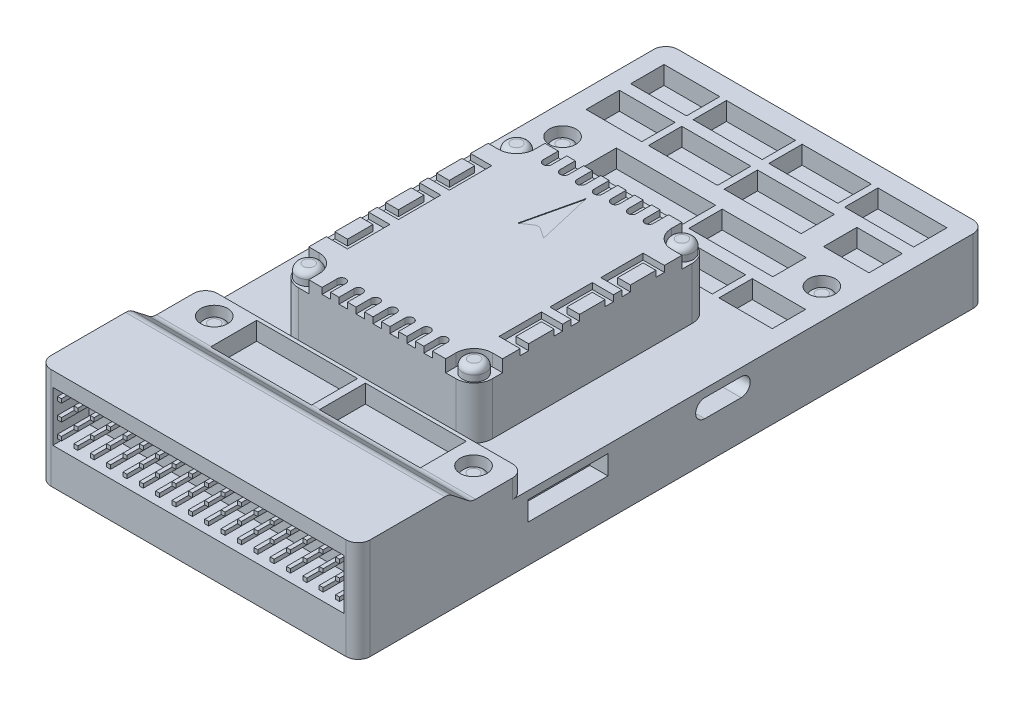
SolidWorks part; units mm, degrees
ref_plane "Front Plane" through (0, 0, 0) normal (0, 0, 1) x (1, 0, 0)
ref_plane "Top Plane" through (0, 0, 0) normal (0, 1, 0) x (1, 0, 0)
ref_plane "Right Plane" through (0, 0, 0) normal (1, 0, 0) x (0, 0, -1)
sketch "Sketch2" plane through (0, 0, 0) normal (1, 0, 0) x (0, 0, -1)
  line L0 (-51.75, 0) -> (51.75, 0)
  line L1 (55, 0) -> (-55, 0) construction
  line L2 (51.75, 0) -> (51.75, 10.7)
  line L3 (51.75, 10.7) -> (-24.25, 10.7)
  line L4 (-24.25, 10.7) -> (-24.25, 13.8)
  line L5 (-24.25, 13.8) -> (-33.05, 13.8)
  line L6 (-33.05, 13.8) -> (-36.75, 16.7)
  line L7 (-36.75, 16.7) -> (-51.75, 16.7)
  line L8 (-51.75, 16.7) -> (-51.75, 0)
  line L9 (0, 55) -> (0, -55) construction
  point P12 (0, 0)
  dimension "D1" = 103.5
  dimension "D2" = 10.7
  dimension "D3" = 16.7
  dimension "D4" = 13.8
  dimension "D5" = 8.8
  dimension "D6" = 27.5
  dimension "D7" = 15
extrude "Boss-Extrude1" add sketch "Sketch2" along normal mid plane 52.7
sketch "Sketch3" plane through (0, 10.7, 0) normal (0, 1, 0) x (1, 0, 0)
  line L0 (0, -9.185) -> (0, 9.185) construction
  line L1 (-16, 16.75) -> (16, 16.75)
  line L2 (-16, 16.75) -> (-16, -22.25)
  line L3 (-16, -22.25) -> (16, -22.25)
  line L4 (16, 16.75) -> (16, -22.25)
  line L5 (26.35, -24.25) -> (-26.35, -24.25) construction
  point P4 (0, 16.75)
  dimension "D1" = 32
  dimension "D2" = 39
  dimension "D3" = 2
extrude "Boss-Extrude2" add sketch "Sketch3" along normal blind 10.6
sketch "Sketch4" plane through (0, 10.7, 0) normal (0, 1, 0) x (1, 0, 0)
  line L0 (26.35, 51.75) -> (26.35, -24.25) construction
  line L1 (-23.35, 48.45) -> (-14.15, 48.45)
  line L2 (-23.35, 48.45) -> (-23.35, 42.95)
  line L3 (-23.35, 42.95) -> (-14.15, 42.95)
  line L4 (-14.15, 48.45) -> (-14.15, 42.95)
  line L5 (-13.05, 48.45) -> (-1.65, 48.45)
  line L6 (-13.05, 48.45) -> (-13.05, 42.95)
  line L7 (-13.05, 42.95) -> (-1.65, 42.95)
  line L8 (-1.65, 48.45) -> (-1.65, 42.95)
  line L9 (-0.55, 48.45) -> (10.85, 48.45)
  line L10 (-0.55, 48.45) -> (-0.55, 42.95)
  line L11 (-0.55, 42.95) -> (10.85, 42.95)
  line L12 (10.85, 48.45) -> (10.85, 42.95)
  line L13 (11.95, 48.45) -> (23.35, 48.45)
  line L14 (11.95, 48.45) -> (11.95, 42.95)
  line L15 (11.95, 42.95) -> (23.35, 42.95)
  line L16 (23.35, 48.45) -> (23.35, 42.95)
  line L17 (-23.35, 41.0757) -> (-14.15, 41.0757)
  line L18 (-23.35, 41.0757) -> (-23.35, 35.5757)
  line L19 (-23.35, 35.5757) -> (-14.15, 35.5757)
  line L20 (-14.15, 41.0757) -> (-14.15, 35.5757)
  line L21 (-13.05, 41.0757) -> (-1.65, 41.0757)
  line L22 (-13.05, 41.0757) -> (-13.05, 35.5757)
  line L23 (-13.05, 35.5757) -> (-1.65, 35.5757)
  line L24 (-1.65, 41.0757) -> (-1.65, 35.5757)
  line L25 (-0.55, 41.0757) -> (12.15, 41.0757)
  line L26 (-0.55, 41.0757) -> (-0.55, 35.5757)
  line L27 (-0.55, 35.5757) -> (12.15, 35.5757)
  line L28 (12.15, 41.0757) -> (12.15, 35.5757)
  line L29 (15.85, 41.0757) -> (23.35, 41.0757)
  line L30 (15.85, 41.0757) -> (15.85, 35.5757)
  line L31 (15.85, 35.5757) -> (23.35, 35.5757)
  line L32 (23.35, 41.0757) -> (23.35, 35.5757)
  line L33 (-15.35, 32.5757) -> (1.03, 32.5757)
  line L34 (-15.35, 32.5757) -> (-15.35, 27.0757)
  line L35 (-15.35, 27.0757) -> (1.03, 27.0757)
  line L36 (1.03, 32.5757) -> (1.03, 27.0757)
  line L37 (2.13, 32.5757) -> (15.98, 32.5757)
  line L38 (2.13, 32.5757) -> (2.13, 27.0757)
  line L39 (2.13, 27.0757) -> (15.98, 27.0757)
  line L40 (15.98, 32.5757) -> (15.98, 27.0757)
  line L41 (-23.35, 25.1102) -> (-14.55, 25.1102)
  line L42 (-23.35, 25.1102) -> (-23.35, 19.6102)
  line L43 (-23.35, 19.6102) -> (-14.55, 19.6102)
  line L44 (-14.55, 25.1102) -> (-14.55, 19.6102)
  line L45 (-13.45, 25.1102) -> (-4.65, 25.1102)
  line L46 (-13.45, 25.1102) -> (-13.45, 19.6102)
  line L47 (-13.45, 19.6102) -> (-4.65, 19.6102)
  line L48 (-4.65, 25.1102) -> (-4.65, 19.6102)
  line L49 (-3.55, 25.1102) -> (13.45, 25.1102)
  line L50 (-3.55, 25.1102) -> (-3.55, 19.6102)
  line L51 (-3.55, 19.6102) -> (13.45, 19.6102)
  line L52 (13.45, 25.1102) -> (13.45, 19.6102)
  line L53 (14.55, 25.1102) -> (23.35, 25.1102)
  line L54 (14.55, 25.1102) -> (14.55, 19.6102)
  line L55 (14.55, 19.6102) -> (23.35, 19.6102)
  line L56 (23.35, 25.1102) -> (23.35, 19.6102)
  line L57 (26.35, 51.75) -> (-26.35, 51.75) construction
  line L58 (-26.35, 51.75) -> (-26.35, -24.25) construction
  dimension "D1" = 3
  dimension "D2" = 3.3
  dimension "D3" = 3
  dimension "D4" = 5.5
  dimension "D5" = 1.8743
  dimension "D6" = 1.9655
  dimension "D7" = 3
  dimension "D8" = 1.1
  dimension "D9" = 1.1
  dimension "D10" = 1.1
  dimension "D11" = 11.4
  dimension "D12" = 12.7
  dimension "D13" = 7.5
  dimension "D14" = 8.8
  dimension "D15" = 1.1
  dimension "D16" = 1.1
  dimension "D17" = 1.1
  dimension "D18" = 16.38
  dimension "D19" = 1.1
  dimension "D20" = 13.85
  dimension "D21" = 10.37
extrude "Cut-Extrude1" cut sketch "Sketch4" against normal blind 3
sketch "Sketch5" plane through (0, 13.8, 0) normal (0, 1, 0) x (1, 0, 0)
  line L0 (-0.65, -24.85) -> (0.65, -24.85) construction
  line L1 (-17.3, -24.85) -> (-0.65, -24.85)
  line L2 (-17.3, -24.85) -> (-17.3, -32.45)
  line L3 (-17.3, -32.45) -> (-0.65, -32.45)
  line L4 (-0.65, -24.85) -> (-0.65, -32.45)
  line L5 (0.65, -24.85) -> (17.3, -24.85)
  line L6 (0.65, -24.85) -> (0.65, -32.45)
  line L7 (0.65, -32.45) -> (17.3, -32.45)
  line L8 (17.3, -24.85) -> (17.3, -32.45)
  line L9 (0, -11.715) -> (0, 11.715) construction
  line L10 (26.35, -24.25) -> (26.35, -33.05) construction
  point P8 (0, -24.85)
  point P14 (26.35, -28.65)
  point P15 (17.3, -28.65)
  dimension "D1" = 34.6
  dimension "D2" = 16.65
  dimension "D3" = 7.6
extrude "Cut-Extrude2" cut sketch "Sketch5" against normal blind 3
sketch "Sketch6" plane through (0, 0, 51.75) normal (0, 0, 1) x (1, 0, 0)
  line L0 (-26.35, 16.7) -> (-26.35, 0) construction
  line L1 (-24.05, 14.3) -> (24.05, 14.3)
  line L2 (-24.05, 14.3) -> (-24.05, 6)
  line L3 (-24.05, 6) -> (24.05, 6)
  line L4 (24.05, 14.3) -> (24.05, 6)
  line L5 (26.35, 16.7) -> (26.35, 0) construction
  line L6 (26.35, 16.7) -> (-26.35, 16.7) construction
  line L7 (28.985, 0) -> (-28.985, 0) construction
  dimension "D1" = 2.3
  dimension "D2" = 2.3
  dimension "D3" = 2.4
  dimension "D4" = 6
extrude "Cut-Extrude3" cut sketch "Sketch6" against normal blind 6
sketch "Sketch7" plane through (0, 0, 45.75) normal (0, 0, 1) x (1, 0, 0)
  line L0 (24.05, 14.3) -> (-24.05, 14.3) construction
  line L1 (-23.2682, 13.3817) -> (-22.6182, 13.3817)
  line L2 (-23.2682, 13.3817) -> (-23.2682, 12.7317)
  line L3 (-23.2682, 12.7317) -> (-22.6182, 12.7317)
  line L4 (-22.6182, 13.3817) -> (-22.6182, 12.7317)
  line L5 (-24.05, 14.3) -> (-24.05, 6) construction
  line L6 (-20.5682, 13.3817) -> (-20.5682, 12.7317)
  line L7 (-20.5682, 13.3817) -> (-19.9182, 13.3817)
  line L8 (-19.9182, 13.3817) -> (-19.9182, 12.7317)
  line L9 (-20.5682, 12.7317) -> (-19.9182, 12.7317)
  line L10 (-17.8682, 13.3817) -> (-17.8682, 12.7317)
  line L11 (-17.8682, 13.3817) -> (-17.2182, 13.3817)
  line L12 (-17.2182, 13.3817) -> (-17.2182, 12.7317)
  line L13 (-17.8682, 12.7317) -> (-17.2182, 12.7317)
  line L14 (-15.1682, 13.3817) -> (-15.1682, 12.7317)
  line L15 (-15.1682, 13.3817) -> (-14.5182, 13.3817)
  line L16 (-14.5182, 13.3817) -> (-14.5182, 12.7317)
  line L17 (-15.1682, 12.7317) -> (-14.5182, 12.7317)
  line L18 (-12.4682, 13.3817) -> (-12.4682, 12.7317)
  line L19 (-12.4682, 13.3817) -> (-11.8182, 13.3817)
  line L20 (-11.8182, 13.3817) -> (-11.8182, 12.7317)
  line L21 (-12.4682, 12.7317) -> (-11.8182, 12.7317)
  line L22 (-9.7682, 13.3817) -> (-9.7682, 12.7317)
  line L23 (-9.7682, 13.3817) -> (-9.1182, 13.3817)
  line L24 (-9.1182, 13.3817) -> (-9.1182, 12.7317)
  line L25 (-9.7682, 12.7317) -> (-9.1182, 12.7317)
  line L26 (-7.0682, 13.3817) -> (-7.0682, 12.7317)
  line L27 (-7.0682, 13.3817) -> (-6.4182, 13.3817)
  line L28 (-6.4182, 13.3817) -> (-6.4182, 12.7317)
  line L29 (-7.0682, 12.7317) -> (-6.4182, 12.7317)
  line L30 (-4.3682, 13.3817) -> (-4.3682, 12.7317)
  line L31 (-4.3682, 13.3817) -> (-3.7182, 13.3817)
  line L32 (-3.7182, 13.3817) -> (-3.7182, 12.7317)
  line L33 (-4.3682, 12.7317) -> (-3.7182, 12.7317)
  line L34 (-1.6682, 13.3817) -> (-1.6682, 12.7317)
  line L35 (-1.6682, 13.3817) -> (-1.0182, 13.3817)
  line L36 (-1.0182, 13.3817) -> (-1.0182, 12.7317)
  line L37 (-1.6682, 12.7317) -> (-1.0182, 12.7317)
  line L38 (1.0318, 13.3817) -> (1.0318, 12.7317)
  line L39 (1.0318, 13.3817) -> (1.6818, 13.3817)
  line L40 (1.6818, 13.3817) -> (1.6818, 12.7317)
  line L41 (1.0318, 12.7317) -> (1.6818, 12.7317)
  line L42 (3.7318, 13.3817) -> (3.7318, 12.7317)
  line L43 (3.7318, 13.3817) -> (4.3818, 13.3817)
  line L44 (4.3818, 13.3817) -> (4.3818, 12.7317)
  line L45 (3.7318, 12.7317) -> (4.3818, 12.7317)
  line L46 (6.4318, 13.3817) -> (6.4318, 12.7317)
  line L47 (6.4318, 13.3817) -> (7.0818, 13.3817)
  line L48 (7.0818, 13.3817) -> (7.0818, 12.7317)
  line L49 (6.4318, 12.7317) -> (7.0818, 12.7317)
  line L50 (9.1318, 13.3817) -> (9.1318, 12.7317)
  line L51 (9.1318, 13.3817) -> (9.7818, 13.3817)
  line L52 (9.7818, 13.3817) -> (9.7818, 12.7317)
  line L53 (9.1318, 12.7317) -> (9.7818, 12.7317)
  line L54 (11.8318, 13.3817) -> (11.8318, 12.7317)
  line L55 (11.8318, 13.3817) -> (12.4818, 13.3817)
  line L56 (12.4818, 13.3817) -> (12.4818, 12.7317)
  line L57 (11.8318, 12.7317) -> (12.4818, 12.7317)
  line L58 (14.5318, 13.3817) -> (14.5318, 12.7317)
  line L59 (14.5318, 13.3817) -> (15.1818, 13.3817)
  line L60 (15.1818, 13.3817) -> (15.1818, 12.7317)
  line L61 (14.5318, 12.7317) -> (15.1818, 12.7317)
  line L62 (17.2318, 13.3817) -> (17.2318, 12.7317)
  line L63 (17.2318, 13.3817) -> (17.8818, 13.3817)
  line L64 (17.8818, 13.3817) -> (17.8818, 12.7317)
  line L65 (17.2318, 12.7317) -> (17.8818, 12.7317)
  line L66 (19.9318, 13.3817) -> (19.9318, 12.7317)
  line L67 (19.9318, 13.3817) -> (20.5818, 13.3817)
  line L68 (20.5818, 13.3817) -> (20.5818, 12.7317)
  line L69 (19.9318, 12.7317) -> (20.5818, 12.7317)
  line L70 (22.6318, 13.3817) -> (22.6318, 12.7317)
  line L71 (22.6318, 13.3817) -> (23.2818, 13.3817)
  line L72 (23.2818, 13.3817) -> (23.2818, 12.7317)
  line L73 (22.6318, 12.7317) -> (23.2818, 12.7317)
  line L74 (-20.5682, 10.6817) -> (-20.5682, 10.0317)
  line L75 (-20.5682, 10.6817) -> (-19.9182, 10.6817)
  line L76 (-19.9182, 10.6817) -> (-19.9182, 10.0317)
  line L77 (-20.5682, 10.0317) -> (-19.9182, 10.0317)
  line L78 (-17.8682, 10.6817) -> (-17.8682, 10.0317)
  line L79 (-17.8682, 10.6817) -> (-17.2182, 10.6817)
  line L80 (-17.2182, 10.6817) -> (-17.2182, 10.0317)
  line L81 (-17.8682, 10.0317) -> (-17.2182, 10.0317)
  line L82 (-15.1682, 10.6817) -> (-15.1682, 10.0317)
  line L83 (-15.1682, 10.6817) -> (-14.5182, 10.6817)
  line L84 (-14.5182, 10.6817) -> (-14.5182, 10.0317)
  line L85 (-15.1682, 10.0317) -> (-14.5182, 10.0317)
  line L86 (-12.4682, 10.6817) -> (-12.4682, 10.0317)
  line L87 (-12.4682, 10.6817) -> (-11.8182, 10.6817)
  line L88 (-11.8182, 10.6817) -> (-11.8182, 10.0317)
  line L89 (-12.4682, 10.0317) -> (-11.8182, 10.0317)
  line L90 (-9.7682, 10.6817) -> (-9.7682, 10.0317)
  line L91 (-9.7682, 10.6817) -> (-9.1182, 10.6817)
  line L92 (-9.1182, 10.6817) -> (-9.1182, 10.0317)
  line L93 (-9.7682, 10.0317) -> (-9.1182, 10.0317)
  line L94 (-7.0682, 10.6817) -> (-7.0682, 10.0317)
  line L95 (-7.0682, 10.6817) -> (-6.4182, 10.6817)
  line L96 (-6.4182, 10.6817) -> (-6.4182, 10.0317)
  line L97 (-7.0682, 10.0317) -> (-6.4182, 10.0317)
  line L98 (-4.3682, 10.6817) -> (-4.3682, 10.0317)
  line L99 (-4.3682, 10.6817) -> (-3.7182, 10.6817)
  line L100 (-3.7182, 10.6817) -> (-3.7182, 10.0317)
  line L101 (-4.3682, 10.0317) -> (-3.7182, 10.0317)
  line L102 (-1.6682, 10.6817) -> (-1.6682, 10.0317)
  line L103 (-1.6682, 10.6817) -> (-1.0182, 10.6817)
  line L104 (-1.0182, 10.6817) -> (-1.0182, 10.0317)
  line L105 (-1.6682, 10.0317) -> (-1.0182, 10.0317)
  line L106 (1.0318, 10.6817) -> (1.0318, 10.0317)
  line L107 (1.0318, 10.6817) -> (1.6818, 10.6817)
  line L108 (1.6818, 10.6817) -> (1.6818, 10.0317)
  line L109 (1.0318, 10.0317) -> (1.6818, 10.0317)
  line L110 (3.7318, 10.6817) -> (3.7318, 10.0317)
  line L111 (3.7318, 10.6817) -> (4.3818, 10.6817)
  line L112 (4.3818, 10.6817) -> (4.3818, 10.0317)
  line L113 (3.7318, 10.0317) -> (4.3818, 10.0317)
  line L114 (6.4318, 10.6817) -> (6.4318, 10.0317)
  line L115 (6.4318, 10.6817) -> (7.0818, 10.6817)
  line L116 (7.0818, 10.6817) -> (7.0818, 10.0317)
  line L117 (6.4318, 10.0317) -> (7.0818, 10.0317)
  line L118 (9.1318, 10.6817) -> (9.1318, 10.0317)
  line L119 (9.1318, 10.6817) -> (9.7818, 10.6817)
  line L120 (9.7818, 10.6817) -> (9.7818, 10.0317)
  line L121 (9.1318, 10.0317) -> (9.7818, 10.0317)
  line L122 (11.8318, 10.6817) -> (11.8318, 10.0317)
  line L123 (11.8318, 10.6817) -> (12.4818, 10.6817)
  line L124 (12.4818, 10.6817) -> (12.4818, 10.0317)
  line L125 (11.8318, 10.0317) -> (12.4818, 10.0317)
  line L126 (14.5318, 10.6817) -> (14.5318, 10.0317)
  line L127 (14.5318, 10.6817) -> (15.1818, 10.6817)
  line L128 (15.1818, 10.6817) -> (15.1818, 10.0317)
  line L129 (14.5318, 10.0317) -> (15.1818, 10.0317)
  line L130 (17.2318, 10.6817) -> (17.2318, 10.0317)
  line L131 (17.2318, 10.6817) -> (17.8818, 10.6817)
  line L132 (17.8818, 10.6817) -> (17.8818, 10.0317)
  line L133 (17.2318, 10.0317) -> (17.8818, 10.0317)
  line L134 (19.9318, 10.6817) -> (19.9318, 10.0317)
  line L135 (19.9318, 10.6817) -> (20.5818, 10.6817)
  line L136 (20.5818, 10.6817) -> (20.5818, 10.0317)
  line L137 (19.9318, 10.0317) -> (20.5818, 10.0317)
  line L138 (22.6318, 10.6817) -> (22.6318, 10.0317)
  line L139 (22.6318, 10.6817) -> (23.2818, 10.6817)
  line L140 (23.2818, 10.6817) -> (23.2818, 10.0317)
  line L141 (22.6318, 10.0317) -> (23.2818, 10.0317)
  line L142 (-20.5682, 7.9817) -> (-20.5682, 7.3317)
  line L143 (-20.5682, 7.9817) -> (-19.9182, 7.9817)
  line L144 (-19.9182, 7.9817) -> (-19.9182, 7.3317)
  line L145 (-20.5682, 7.3317) -> (-19.9182, 7.3317)
  line L146 (-17.8682, 7.9817) -> (-17.8682, 7.3317)
  line L147 (-17.8682, 7.9817) -> (-17.2182, 7.9817)
  line L148 (-17.2182, 7.9817) -> (-17.2182, 7.3317)
  line L149 (-17.8682, 7.3317) -> (-17.2182, 7.3317)
  line L150 (-15.1682, 7.9817) -> (-15.1682, 7.3317)
  line L151 (-15.1682, 7.9817) -> (-14.5182, 7.9817)
  line L152 (-14.5182, 7.9817) -> (-14.5182, 7.3317)
  line L153 (-15.1682, 7.3317) -> (-14.5182, 7.3317)
  line L154 (-12.4682, 7.9817) -> (-12.4682, 7.3317)
  line L155 (-12.4682, 7.9817) -> (-11.8182, 7.9817)
  line L156 (-11.8182, 7.9817) -> (-11.8182, 7.3317)
  line L157 (-12.4682, 7.3317) -> (-11.8182, 7.3317)
  line L158 (-9.7682, 7.9817) -> (-9.7682, 7.3317)
  line L159 (-9.7682, 7.9817) -> (-9.1182, 7.9817)
  line L160 (-9.1182, 7.9817) -> (-9.1182, 7.3317)
  line L161 (-9.7682, 7.3317) -> (-9.1182, 7.3317)
  line L162 (-7.0682, 7.9817) -> (-7.0682, 7.3317)
  line L163 (-7.0682, 7.9817) -> (-6.4182, 7.9817)
  line L164 (-6.4182, 7.9817) -> (-6.4182, 7.3317)
  line L165 (-7.0682, 7.3317) -> (-6.4182, 7.3317)
  line L166 (-4.3682, 7.9817) -> (-4.3682, 7.3317)
  line L167 (-4.3682, 7.9817) -> (-3.7182, 7.9817)
  line L168 (-3.7182, 7.9817) -> (-3.7182, 7.3317)
  line L169 (-4.3682, 7.3317) -> (-3.7182, 7.3317)
  line L170 (-1.6682, 7.9817) -> (-1.6682, 7.3317)
  line L171 (-1.6682, 7.9817) -> (-1.0182, 7.9817)
  line L172 (-1.0182, 7.9817) -> (-1.0182, 7.3317)
  line L173 (-1.6682, 7.3317) -> (-1.0182, 7.3317)
  line L174 (1.0318, 7.9817) -> (1.0318, 7.3317)
  line L175 (1.0318, 7.9817) -> (1.6818, 7.9817)
  line L176 (1.6818, 7.9817) -> (1.6818, 7.3317)
  line L177 (1.0318, 7.3317) -> (1.6818, 7.3317)
  line L178 (3.7318, 7.9817) -> (3.7318, 7.3317)
  line L179 (3.7318, 7.9817) -> (4.3818, 7.9817)
  line L180 (4.3818, 7.9817) -> (4.3818, 7.3317)
  line L181 (3.7318, 7.3317) -> (4.3818, 7.3317)
  line L182 (6.4318, 7.9817) -> (6.4318, 7.3317)
  line L183 (6.4318, 7.9817) -> (7.0818, 7.9817)
  line L184 (7.0818, 7.9817) -> (7.0818, 7.3317)
  line L185 (6.4318, 7.3317) -> (7.0818, 7.3317)
  line L186 (9.1318, 7.9817) -> (9.1318, 7.3317)
  line L187 (9.1318, 7.9817) -> (9.7818, 7.9817)
  line L188 (9.7818, 7.9817) -> (9.7818, 7.3317)
  line L189 (9.1318, 7.3317) -> (9.7818, 7.3317)
  line L190 (11.8318, 7.9817) -> (11.8318, 7.3317)
  line L191 (11.8318, 7.9817) -> (12.4818, 7.9817)
  line L192 (12.4818, 7.9817) -> (12.4818, 7.3317)
  line L193 (11.8318, 7.3317) -> (12.4818, 7.3317)
  line L194 (14.5318, 7.9817) -> (14.5318, 7.3317)
  line L195 (14.5318, 7.9817) -> (15.1818, 7.9817)
  line L196 (15.1818, 7.9817) -> (15.1818, 7.3317)
  line L197 (14.5318, 7.3317) -> (15.1818, 7.3317)
  line L198 (17.2318, 7.9817) -> (17.2318, 7.3317)
  line L199 (17.2318, 7.9817) -> (17.8818, 7.9817)
  line L200 (17.8818, 7.9817) -> (17.8818, 7.3317)
  line L201 (17.2318, 7.3317) -> (17.8818, 7.3317)
  line L202 (19.9318, 7.9817) -> (19.9318, 7.3317)
  line L203 (19.9318, 7.9817) -> (20.5818, 7.9817)
  line L204 (20.5818, 7.9817) -> (20.5818, 7.3317)
  line L205 (19.9318, 7.3317) -> (20.5818, 7.3317)
  line L206 (22.6318, 7.9817) -> (22.6318, 7.3317)
  line L207 (22.6318, 7.9817) -> (23.2818, 7.9817)
  line L208 (23.2818, 7.9817) -> (23.2818, 7.3317)
  line L209 (22.6318, 7.3317) -> (23.2818, 7.3317)
  line L210 (-23.2682, 10.6817) -> (-23.2682, 10.0317)
  line L211 (-23.2682, 10.6817) -> (-22.6182, 10.6817)
  line L212 (-22.6182, 10.6817) -> (-22.6182, 10.0317)
  line L213 (-23.2682, 10.0317) -> (-22.6182, 10.0317)
  line L214 (-23.2682, 7.9817) -> (-23.2682, 7.3317)
  line L215 (-23.2682, 7.9817) -> (-22.6182, 7.9817)
  line L216 (-22.6182, 7.9817) -> (-22.6182, 7.3317)
  line L217 (-23.2682, 7.3317) -> (-22.6182, 7.3317)
  dimension "D1" = 0.65
  dimension "D2" = 0.9183
  dimension "D3" = 0.7818
  dimension "D6" = 2.05
  dimension "D7" = 2.05
  dimension "D4" = 18
  dimension "D5" = 3
extrude "Boss-Extrude3" add sketch "Sketch7" along normal blind 6
sketch "Sketch8" plane through (-26.35, 0, 0) normal (-1, 0, 0) x (0, 0, 1)
  line L0 (51.75, 16.7) -> (51.75, 0) construction
  line L1 (10.45, 9.4) -> (23.75, 9.4)
  line L2 (10.45, 9.4) -> (10.45, 6.1)
  line L3 (10.45, 6.1) -> (23.75, 6.1)
  line L4 (23.75, 9.4) -> (23.75, 6.1)
  line L5 (-51.75, 10.7) -> (24.25, 10.7) construction
  dimension "D1" = 3.3
  dimension "D2" = 13.3
  dimension "D3" = 28
  dimension "D4" = 1.3
extrude "Cut-Extrude4" cut sketch "Sketch8" against normal blind 3
sketch "Sketch9" plane through (26.35, 0, 0) normal (1, 0, 0) x (0, 0, -1)
  line L0 (51.75, 10.7) -> (-24.25, 10.7) construction
  line L1 (-23.75, 9.4) -> (-10.5, 9.4)
  line L2 (-23.75, 9.4) -> (-23.75, 6.2)
  line L3 (-23.75, 6.2) -> (-10.5, 6.2)
  line L4 (-10.5, 9.4) -> (-10.5, 6.2)
  line L5 (-51.75, 16.7) -> (-51.75, 0) construction
  line L6 (5.47, 7.9) -> (11.47, 7.9) construction
  line L7 (5.47, 9.4) -> (11.47, 9.4)
  line L8 (5.47, 6.4) -> (11.47, 6.4)
  arc A0 (5.47, 9.4) -> (5.47, 6.4) centre (5.47, 7.9) ccw
  arc A1 (11.47, 6.4) -> (11.47, 9.4) centre (11.47, 7.9) ccw
  point P10 (8.47, 7.9)
  dimension "D1" = 13.25
  dimension "D2" = 3.2
  dimension "D3" = 1.3
  dimension "D4" = 28
  dimension "D5" = 6
  dimension "D6" = 3
  dimension "D7" = 15.97
  dimension "D8" = 1.3
extrude "Cut-Extrude5" cut sketch "Sketch9" against normal blind 3
sketch "Sketch10" plane through (0, 0, 0) normal (0, -1, 0) x (1, 0, 0)
  line L0 (0, -11.715) -> (0, 11.715) construction
  line L1 (-21.4, 27.75) -> (21.4, 27.75) construction
  line L2 (-21.4, 27.75) -> (-21.4, -29.75) construction
  line L3 (-21.4, -29.75) -> (21.4, -29.75) construction
  line L4 (21.4, 27.75) -> (21.4, -29.75) construction
  line L6 (26.35, -51.75) -> (-26.35, -51.75) construction
  circle A0 centre (-21.4, 27.75) radius 1.25
  circle A1 centre (21.4, 27.75) radius 1.25
  circle A2 centre (21.4, -29.75) radius 1.25
  circle A3 centre (-21.4, -29.75) radius 1.25
  point P8 (0, 27.75)
  dimension "D3" = 2.5
  dimension "D1" = 57.5
  dimension "D2" = 42.8
  dimension "D4" = 22
extrude "Cut-Extrude6" cut sketch "Sketch10" against normal blind 3
sketch "Sketch11" plane through (0, 0, 0) normal (0, -1, 0) x (1, 0, 0)
  line L0 (0, -11.715) -> (0, 11.715) construction
  line L1 (-12.25, 17.75) -> (12.25, 17.75) construction
  line L2 (-12.25, 17.75) -> (-12.25, -13.75) construction
  line L3 (-12.25, -13.75) -> (12.25, -13.75) construction
  line L4 (12.25, 17.75) -> (12.25, -13.75) construction
  line L5 (26.35, -51.75) -> (-26.35, -51.75) construction
  circle A0 centre (-12.25, 17.75) radius 2.2
  circle A1 centre (12.25, 17.75) radius 2.2
  circle A2 centre (12.25, -13.75) radius 2.2
  circle A3 centre (-12.25, -13.75) radius 2.2
  point P4 (0, 17.75)
  dimension "D1" = 4.4
  dimension "D2" = 31.5
  dimension "D3" = 24.5
  dimension "D4" = 38
extrude "Cut-Extrude7" cut sketch "Sketch11" against normal blind 3
fillet "Fillet1" radius 2 8 edges at (0, 13.8, 33.05) (0, 16.7, 36.75) (26.35, 5.35, -51.75) (26.35, 8.35, 51.75) (-26.35, 8.35, 51.75) (-26.35, 5.35, -51.75) (26.35, 12.25, 24.25) (-26.35, 12.25, 24.25)
fillet "Fillet2" radius 3 4 edges at (-16, 16, -16.75) (-16, 16, 22.25) (16, 16, 22.25) (16, 16, -16.75)
sketch "Sketch12" plane through (0, 21.3, 0) normal (0, 1, 0) x (1, 0, 0)
  line L0 (-8.4, 16.75) -> (-8.4, 14.25) construction
  line L1 (13, 16.75) -> (-13, 16.75) construction
  line L2 (-7.7, 16.75) -> (-7.7, 14.25)
  line L3 (-9.1, 16.75) -> (-9.1, 14.25)
  line L4 (-5.6, 16.75) -> (-5.6, 14.25) construction
  line L5 (-4.9, 16.75) -> (-4.9, 14.25)
  line L6 (-6.3, 16.75) -> (-6.3, 14.25)
  line L7 (-2.8, 16.75) -> (-2.8, 14.25) construction
  line L8 (-2.1, 16.75) -> (-2.1, 14.25)
  line L9 (-3.5, 16.75) -> (-3.5, 14.25)
  line L10 (0, 16.75) -> (0, 14.25) construction
  line L11 (0.7, 16.75) -> (0.7, 14.25)
  line L12 (-0.7, 16.75) -> (-0.7, 14.25)
  line L13 (2.8, 16.75) -> (2.8, 14.25) construction
  line L14 (3.5, 16.75) -> (3.5, 14.25)
  line L15 (2.1, 16.75) -> (2.1, 14.25)
  line L16 (5.6, 16.75) -> (5.6, 14.25) construction
  line L17 (6.3, 16.75) -> (6.3, 14.25)
  line L18 (4.9, 16.75) -> (4.9, 14.25)
  line L19 (8.4, 16.75) -> (8.4, 14.25) construction
  line L20 (9.1, 16.75) -> (9.1, 14.25)
  line L21 (7.7, 16.75) -> (7.7, 14.25)
  line L22 (0, -11.715) -> (0, 11.715) construction
  line L23 (13, 16.75) -> (-13, 16.75) construction
  line L26 (-13.7846, -2.75) -> (10.4131, -2.75) construction
  line L27 (-16, 13.75) -> (-16, -19.25) construction
  line L28 (-8.4, -22.25) -> (-8.4, -19.75) construction
  line L29 (-7.7, -22.25) -> (-7.7, -19.75)
  line L30 (-9.1, -22.25) -> (-9.1, -19.75)
  line L31 (-5.6, -22.25) -> (-5.6, -19.75) construction
  line L32 (-4.9, -22.25) -> (-4.9, -19.75)
  line L33 (-6.3, -22.25) -> (-6.3, -19.75)
  line L34 (-2.8, -22.25) -> (-2.8, -19.75) construction
  line L35 (-2.1, -22.25) -> (-2.1, -19.75)
  line L36 (-3.5, -22.25) -> (-3.5, -19.75)
  line L37 (0, -22.25) -> (0, -19.75) construction
  line L38 (0.7, -22.25) -> (0.7, -19.75)
  line L39 (-0.7, -22.25) -> (-0.7, -19.75)
  line L40 (2.8, -22.25) -> (2.8, -19.75) construction
  line L41 (3.5, -22.25) -> (3.5, -19.75)
  line L42 (2.1, -22.25) -> (2.1, -19.75)
  line L43 (5.6, -22.25) -> (5.6, -19.75) construction
  line L44 (6.3, -22.25) -> (6.3, -19.75)
  line L45 (4.9, -22.25) -> (4.9, -19.75)
  line L46 (8.4, -22.25) -> (8.4, -19.75) construction
  line L47 (9.1, -22.25) -> (9.1, -19.75)
  line L48 (7.7, -22.25) -> (7.7, -19.75)
  arc A0 (-7.7, 16.75) -> (-9.1, 16.75) centre (-8.4, 16.75) ccw
  arc A1 (-9.1, 14.25) -> (-7.7, 14.25) centre (-8.4, 14.25) ccw
  arc A2 (-4.9, 16.75) -> (-6.3, 16.75) centre (-5.6, 16.75) ccw
  arc A3 (-6.3, 14.25) -> (-4.9, 14.25) centre (-5.6, 14.25) ccw
  arc A4 (-2.1, 16.75) -> (-3.5, 16.75) centre (-2.8, 16.75) ccw
  arc A5 (-3.5, 14.25) -> (-2.1, 14.25) centre (-2.8, 14.25) ccw
  arc A6 (0.7, 16.75) -> (-0.7, 16.75) centre (0, 16.75) ccw
  arc A7 (-0.7, 14.25) -> (0.7, 14.25) centre (0, 14.25) ccw
  arc A8 (3.5, 16.75) -> (2.1, 16.75) centre (2.8, 16.75) ccw
  arc A9 (2.1, 14.25) -> (3.5, 14.25) centre (2.8, 14.25) ccw
  arc A10 (6.3, 16.75) -> (4.9, 16.75) centre (5.6, 16.75) ccw
  arc A11 (4.9, 14.25) -> (6.3, 14.25) centre (5.6, 14.25) ccw
  arc A12 (9.1, 16.75) -> (7.7, 16.75) centre (8.4, 16.75) ccw
  arc A13 (7.7, 14.25) -> (9.1, 14.25) centre (8.4, 14.25) ccw
  arc A14 (-7.7, -22.25) -> (-9.1, -22.25) centre (-8.4, -22.25) cw
  arc A15 (-9.1, -19.75) -> (-7.7, -19.75) centre (-8.4, -19.75) cw
  arc A16 (-4.9, -22.25) -> (-6.3, -22.25) centre (-5.6, -22.25) cw
  arc A17 (-6.3, -19.75) -> (-4.9, -19.75) centre (-5.6, -19.75) cw
  arc A18 (-2.1, -22.25) -> (-3.5, -22.25) centre (-2.8, -22.25) cw
  arc A19 (-3.5, -19.75) -> (-2.1, -19.75) centre (-2.8, -19.75) cw
  arc A20 (0.7, -22.25) -> (-0.7, -22.25) centre (0, -22.25) cw
  arc A21 (-0.7, -19.75) -> (0.7, -19.75) centre (0, -19.75) cw
  arc A22 (3.5, -22.25) -> (2.1, -22.25) centre (2.8, -22.25) cw
  arc A23 (2.1, -19.75) -> (3.5, -19.75) centre (2.8, -19.75) cw
  arc A24 (6.3, -22.25) -> (4.9, -22.25) centre (5.6, -22.25) cw
  arc A25 (4.9, -19.75) -> (6.3, -19.75) centre (5.6, -19.75) cw
  arc A26 (9.1, -22.25) -> (7.7, -22.25) centre (8.4, -22.25) cw
  arc A27 (7.7, -19.75) -> (9.1, -19.75) centre (8.4, -19.75) cw
  point P4 (-8.4, 15.5)
  point P12 (-5.6, 15.5)
  point P19 (-2.8, 15.5)
  point P26 (0, 15.5)
  point P33 (2.8, 15.5)
  point P40 (5.6, 15.5)
  point P47 (8.4, 15.5)
  point P58 (-16, -2.75)
  point P63 (-8.4, -21)
  point P70 (-5.6, -21)
  point P77 (-2.8, -21)
  point P84 (0, -21)
  point P91 (2.8, -21)
  point P98 (5.6, -21)
  point P105 (8.4, -21)
  dimension "D1" = 1.4
  dimension "D2" = 2.5
  dimension "D4" = 1.4
  dimension "D3" = 7
extrude "Cut-Extrude8" cut sketch "Sketch12" against normal blind 1
sketch "Sketch13" plane through (0, 21.3, 0) normal (0, 1, 0) x (1, 0, 0)
  line L0 (-16, 13.75) -> (-16, -19.25) construction
  line L1 (-18.8, 9.15) -> (-12.5, 9.15)
  line L2 (-18.8, 9.15) -> (-18.8, 2.15)
  line L3 (-18.8, 2.15) -> (-12.5, 2.15)
  line L4 (-12.5, 9.15) -> (-12.5, 2.15)
  line L5 (-17.4, 7.75) -> (-13.9, 7.75)
  line L6 (-17.4, 7.75) -> (-17.4, 3.55)
  line L7 (-17.4, 3.55) -> (-13.9, 3.55)
  line L8 (-13.9, 7.75) -> (-13.9, 3.55)
  line L9 (-18.8, 0.75) -> (-12.5, 0.75)
  line L10 (-18.8, 0.75) -> (-18.8, -6.25)
  line L11 (-18.8, -6.25) -> (-12.5, -6.25)
  line L12 (-12.5, 0.75) -> (-12.5, -6.25)
  line L13 (-17.4, -0.65) -> (-13.9, -0.65)
  line L14 (-17.4, -0.65) -> (-17.4, -4.85)
  line L15 (-17.4, -4.85) -> (-13.9, -4.85)
  line L16 (-13.9, -0.65) -> (-13.9, -4.85)
  line L17 (-18.8, -7.65) -> (-12.5, -7.65)
  line L18 (-18.8, -7.65) -> (-18.8, -14.65)
  line L19 (-18.8, -14.65) -> (-12.5, -14.65)
  line L20 (-12.5, -7.65) -> (-12.5, -14.65)
  line L21 (-17.4, -9.05) -> (-13.9, -9.05)
  line L22 (-17.4, -9.05) -> (-17.4, -13.25)
  line L23 (-17.4, -13.25) -> (-13.9, -13.25)
  line L24 (-13.9, -9.05) -> (-13.9, -13.25)
  line L26 (-16, 13.75) -> (-16, -19.25) construction
  line L27 (0, 12.7067) -> (0, -15.9505) construction
  line L28 (0, -11.715) -> (0, 11.715) construction
  line L29 (13.9, -9.05) -> (13.9, -13.25)
  line L30 (17.4, -13.25) -> (13.9, -13.25)
  line L31 (17.4, -9.05) -> (17.4, -13.25)
  line L32 (17.4, -9.05) -> (13.9, -9.05)
  line L33 (12.5, -7.65) -> (12.5, -14.65)
  line L34 (18.8, -14.65) -> (12.5, -14.65)
  line L35 (18.8, -7.65) -> (18.8, -14.65)
  line L36 (18.8, -7.65) -> (12.5, -7.65)
  line L37 (13.9, -0.65) -> (13.9, -4.85)
  line L38 (17.4, -4.85) -> (13.9, -4.85)
  line L39 (17.4, -0.65) -> (17.4, -4.85)
  line L40 (17.4, -0.65) -> (13.9, -0.65)
  line L41 (12.5, 0.75) -> (12.5, -6.25)
  line L42 (18.8, -6.25) -> (12.5, -6.25)
  line L43 (18.8, 0.75) -> (18.8, -6.25)
  line L44 (18.8, 0.75) -> (12.5, 0.75)
  line L45 (13.9, 7.75) -> (13.9, 3.55)
  line L46 (17.4, 3.55) -> (13.9, 3.55)
  line L47 (17.4, 7.75) -> (17.4, 3.55)
  line L48 (17.4, 7.75) -> (13.9, 7.75)
  line L49 (12.5, 9.15) -> (12.5, 2.15)
  line L50 (18.8, 2.15) -> (12.5, 2.15)
  line L51 (18.8, 9.15) -> (18.8, 2.15)
  line L52 (18.8, 9.15) -> (12.5, 9.15)
  point P10 (-16, -2.75)
  point P27 (-18.8, -2.75)
  dimension "D1" = 1.4
  dimension "D2" = 1.4
  dimension "D3" = 1.4
  dimension "D4" = 1.4
  dimension "D5" = 1.4
  dimension "D7" = 1.4
  dimension "D8" = 7
  dimension "D9" = 3.5
  dimension "D6" = 3
extrude "Cut-Extrude9" cut sketch "Sketch13" against normal blind 1
sketch "Sketch14" plane through (0, 21.3, 0) normal (0, 1, 0) x (1, 0, 0)
  line L0 (-16, 12.05) -> (-14.3, 12.05)
  line L1 (-16, 13.75) -> (-16, 9.15) construction
  line L2 (-11.3, 15.05) -> (-11.3, 16.75)
  line L3 (-9.1, 16.75) -> (-13, 16.75) construction
  line L4 (-16, 13.75) -> (-16, -19.25) construction
  line L5 (-12.5, -2.75) -> (12.5, -2.75) construction
  line L6 (-12.5, -6.25) -> (-12.5, 0.75) construction
  line L7 (12.5, 0.75) -> (12.5, -6.25) construction
  line L8 (0, 12.05) -> (0, -14.6697) construction
  line L9 (0, -11.715) -> (0, 11.715) construction
  line L10 (11.3, 15.05) -> (11.3, 16.75)
  line L11 (16, 12.05) -> (14.3, 12.05)
  line L12 (16, -17.55) -> (14.3, -17.55)
  line L13 (11.3, -20.55) -> (11.3, -22.25)
  line L14 (-11.3, -20.55) -> (-11.3, -22.25)
  line L15 (-16, -17.55) -> (-14.3, -17.55)
  line L86 (12.5, 9.15) -> (16, 9.15)
  line L87 (16, 9.15) -> (16, 13.75)
  line L88 (13, 16.75) -> (9.1, 16.75)
  line L89 (9.1, 16.75) -> (9.1, 14.25)
  line L90 (7.7, 14.25) -> (7.7, 16.75)
  line L91 (7.7, 16.75) -> (6.3, 16.75)
  line L92 (6.3, 16.75) -> (6.3, 14.25)
  line L93 (4.9, 14.25) -> (4.9, 16.75)
  line L94 (4.9, 16.75) -> (3.5, 16.75)
  line L95 (3.5, 16.75) -> (3.5, 14.25)
  line L96 (2.1, 14.25) -> (2.1, 16.75)
  line L97 (2.1, 16.75) -> (0.7, 16.75)
  line L98 (0.7, 16.75) -> (0.7, 14.25)
  line L99 (-0.7, 14.25) -> (-0.7, 16.75)
  line L100 (-0.7, 16.75) -> (-2.1, 16.75)
  line L101 (-2.1, 16.75) -> (-2.1, 14.25)
  line L102 (-3.5, 14.25) -> (-3.5, 16.75)
  line L103 (-3.5, 16.75) -> (-4.9, 16.75)
  line L104 (-4.9, 16.75) -> (-4.9, 14.25)
  line L105 (-6.3, 14.25) -> (-6.3, 16.75)
  line L106 (-6.3, 16.75) -> (-7.7, 16.75)
  line L107 (-7.7, 16.75) -> (-7.7, 14.25)
  line L108 (-9.1, 14.25) -> (-9.1, 16.75)
  line L109 (-9.1, 16.75) -> (-13, 16.75)
  line L110 (-16, 13.75) -> (-16, 9.15)
  line L111 (-16, 9.15) -> (-12.5, 9.15)
  line L112 (-12.5, 9.15) -> (-12.5, 2.15)
  line L113 (-12.5, 2.15) -> (-16, 2.15)
  line L114 (-16, 2.15) -> (-16, 0.75)
  line L115 (-16, 0.75) -> (-12.5, 0.75)
  line L116 (-12.5, 0.75) -> (-12.5, -6.25)
  line L117 (-12.5, -6.25) -> (-16, -6.25)
  line L118 (-16, -6.25) -> (-16, -7.65)
  line L119 (-16, -7.65) -> (-12.5, -7.65)
  line L120 (-12.5, -7.65) -> (-12.5, -14.65)
  line L121 (-12.5, -14.65) -> (-16, -14.65)
  line L122 (-16, -14.65) -> (-16, -19.25)
  line L123 (-13, -22.25) -> (-9.1, -22.25)
  line L124 (-9.1, -22.25) -> (-9.1, -19.75)
  line L125 (-7.7, -19.75) -> (-7.7, -22.25)
  line L126 (-7.7, -22.25) -> (-6.3, -22.25)
  line L127 (-6.3, -22.25) -> (-6.3, -19.75)
  line L128 (-4.9, -19.75) -> (-4.9, -22.25)
  line L129 (-4.9, -22.25) -> (-3.5, -22.25)
  line L130 (-3.5, -22.25) -> (-3.5, -19.75)
  line L131 (-2.1, -19.75) -> (-2.1, -22.25)
  line L132 (-2.1, -22.25) -> (-0.7, -22.25)
  line L133 (-0.7, -22.25) -> (-0.7, -19.75)
  line L134 (0.7, -19.75) -> (0.7, -22.25)
  line L135 (0.7, -22.25) -> (2.1, -22.25)
  line L136 (2.1, -22.25) -> (2.1, -19.75)
  line L137 (3.5, -19.75) -> (3.5, -22.25)
  line L138 (3.5, -22.25) -> (4.9, -22.25)
  line L139 (4.9, -22.25) -> (4.9, -19.75)
  line L140 (6.3, -19.75) -> (6.3, -22.25)
  line L141 (6.3, -22.25) -> (7.7, -22.25)
  line L142 (7.7, -22.25) -> (7.7, -19.75)
  line L143 (9.1, -19.75) -> (9.1, -22.25)
  line L144 (9.1, -22.25) -> (13, -22.25)
  line L145 (16, -19.25) -> (16, -14.65)
  line L146 (16, -14.65) -> (12.5, -14.65)
  line L147 (12.5, -14.65) -> (12.5, -7.65)
  line L148 (12.5, -7.65) -> (16, -7.65)
  line L149 (16, -7.65) -> (16, -6.25)
  line L150 (16, -6.25) -> (12.5, -6.25)
  line L151 (12.5, -6.25) -> (12.5, 0.75)
  line L152 (12.5, 0.75) -> (16, 0.75)
  line L153 (16, 0.75) -> (16, 2.15)
  line L154 (16, 2.15) -> (12.5, 2.15)
  line L155 (12.5, 2.15) -> (12.5, 9.15)
  line L157 (16, 12.05) -> (16, 13.75)
  line L158 (13, 16.75) -> (11.3, 16.75)
  line L179 (-11.3, 16.75) -> (-13, 16.75)
  line L180 (-16, 13.75) -> (-16, 12.05)
  line L192 (-16, -17.55) -> (-16, -19.25)
  line L193 (-13, -22.25) -> (-11.3, -22.25)
  line L214 (11.3, -22.25) -> (13, -22.25)
  line L215 (16, -19.25) -> (16, -17.55)
  arc A0 (-11.3, 15.05) -> (-14.3, 12.05) centre (-14.3, 15.05) cw
  arc A1 (11.3, 15.05) -> (14.3, 12.05) centre (14.3, 15.05) ccw
  arc A2 (11.3, -20.55) -> (14.3, -17.55) centre (14.3, -20.55) cw
  arc A3 (-11.3, -20.55) -> (-14.3, -17.55) centre (-14.3, -20.55) ccw
  arc A22 (16, 13.75) -> (13, 16.75) centre (13, 13.75) ccw
  arc A23 (7.7, 14.25) -> (9.1, 14.25) centre (8.4, 14.25) ccw
  arc A24 (4.9, 14.25) -> (6.3, 14.25) centre (5.6, 14.25) ccw
  arc A25 (2.1, 14.25) -> (3.5, 14.25) centre (2.8, 14.25) ccw
  arc A26 (-0.7, 14.25) -> (0.7, 14.25) centre (0, 14.25) ccw
  arc A27 (-3.5, 14.25) -> (-2.1, 14.25) centre (-2.8, 14.25) ccw
  arc A28 (-6.3, 14.25) -> (-4.9, 14.25) centre (-5.6, 14.25) ccw
  arc A29 (-9.1, 14.25) -> (-7.7, 14.25) centre (-8.4, 14.25) ccw
  arc A30 (-13, 16.75) -> (-16, 13.75) centre (-13, 13.75) ccw
  arc A31 (-16, -19.25) -> (-13, -22.25) centre (-13, -19.25) ccw
  arc A32 (-7.7, -19.75) -> (-9.1, -19.75) centre (-8.4, -19.75) ccw
  arc A33 (-4.9, -19.75) -> (-6.3, -19.75) centre (-5.6, -19.75) ccw
  arc A34 (-2.1, -19.75) -> (-3.5, -19.75) centre (-2.8, -19.75) ccw
  arc A35 (0.7, -19.75) -> (-0.7, -19.75) centre (0, -19.75) ccw
  arc A36 (3.5, -19.75) -> (2.1, -19.75) centre (2.8, -19.75) ccw
  arc A37 (6.3, -19.75) -> (4.9, -19.75) centre (5.6, -19.75) ccw
  arc A38 (9.1, -19.75) -> (7.7, -19.75) centre (8.4, -19.75) ccw
  arc A39 (13, -22.25) -> (16, -19.25) centre (13, -19.25) ccw
  arc A40 (16, 13.75) -> (13, 16.75) centre (13, 13.75) ccw
  arc A48 (-13, 16.75) -> (-16, 13.75) centre (-13, 13.75) ccw
  arc A49 (-16, -19.25) -> (-13, -22.25) centre (-13, -19.25) ccw
  arc A57 (13, -22.25) -> (16, -19.25) centre (13, -19.25) ccw
  dimension "D1" = 3
  dimension "D2" = 4.7
  dimension "D3" = 4.7
  dimension "D4" = 0
extrude "Cut-Extrude10" cut sketch "Sketch14" against normal blind 2 and the other way through all
sketch "Sketch15" plane through (0, 19.3, 0) normal (0, 1, 0) x (1, 0, 0)
  line L0 (-16, -17.55) -> (-11.3, -22.25) construction
  line L1 (-12.5, -2.75) -> (12.5, -2.75) construction
  line L2 (-12.5, -6.25) -> (-12.5, 0.75) construction
  line L3 (12.5, 0.75) -> (12.5, -6.25) construction
  line L4 (0, 9.6281) -> (0, -10.503) construction
  line L5 (0, -11.715) -> (0, 11.715) construction
  circle A0 centre (-13.65, -19.9) radius 1.9
  circle A1 centre (13.65, -19.9) radius 1.9
  circle A2 centre (13.65, 14.4) radius 1.9
  circle A3 centre (-13.65, 14.4) radius 1.9
  point P3 (-13.65, -19.9)
  dimension "D1" = 3.8
other "Pen Sketch1" parameters "D1"=2.7599
extrude "Boss-Extrude4" add sketch "Sketch15" along normal blind 2
fillet "Fillet3" radius 1 4 edges at (-13.65, 21.3, 21.8) (13.65, 21.3, 18) (13.65, 21.3, -12.5) (-13.65, 21.3, -16.3)
sketch "Sketch17" plane through (0, 13.8, 0) normal (0, 1, 0) x (1, 0, 0)
  circle A0 centre (-21.4, -27.75) radius 2.2
  circle A1 centre (21.4, -27.75) radius 2.2
  circle A2 centre (21.4, 29.75) radius 2.2
  circle A3 centre (-21.4, 29.75) radius 2.2
  circle A4 centre (-21.4, 29.75) radius 1.25 construction
  circle A5 centre (21.4, 29.75) radius 1.25 construction
  circle A6 centre (21.4, -27.75) radius 1.25 construction
  circle A7 centre (-21.4, -27.75) radius 1.25 construction
  dimension "D1" = 4.4
extrude "Cut-Extrude11" cut sketch "Sketch17" against normal blind 3
sketch "Sketch18" plane through (0, 10.7, 0) normal (0, 1, 0) x (1, 0, 0)
  circle A0 centre (-21.4, 29.75) radius 2.2
  circle A1 centre (21.4, 29.75) radius 2.2
  circle A2 centre (-21.4, 29.75) radius 1.25 construction
  circle A3 centre (21.4, 29.75) radius 1.25 construction
  dimension "D1" = 4.4
extrude "Cut-Extrude12" cut sketch "Sketch18" against normal blind 3
sketch "Sketch19" plane through (0, 7.7, 0) normal (0, 1, 0) x (1, 0, 0)
  circle A0 centre (-21.4, 29.75) radius 1.9
  circle A1 centre (21.4, 29.75) radius 1.9
  circle A2 centre (21.4, 29.75) radius 2.2 construction
  circle A3 centre (-21.4, 29.75) radius 2.2 construction
  dimension "D1" = 3.8
extrude "Boss-Extrude5" add sketch "Sketch19" along normal blind 2
sketch "Sketch20" plane through (0, 10.8, 0) normal (0, 1, 0) x (1, 0, 0)
  circle A0 centre (-21.4, -27.75) radius 1.9
  circle A1 centre (21.4, -27.75) radius 1.9
  circle A2 centre (-21.4, -27.75) radius 2.2 construction
  circle A3 centre (21.4, -27.75) radius 2.2 construction
  dimension "D1" = 3.8
  dimension "D2" = 3.8
extrude "Boss-Extrude6" add sketch "Sketch20" along normal blind 2
fillet "Fillet4" radius 1 4 edges at (-21.4, 12.8, 29.65) (21.4, 12.8, 29.65) (21.4, 9.7, -27.85) (-21.4, 9.7, -27.85)
sketch "Sketch21" plane through (0, 21.3, 0) normal (0, 1, 0) x (1, 0, 0)
  line L0 (0, 12.2768) -> (-2.15, 3.0768)
  line L1 (0, -11.715) -> (0, 11.715) construction
  line L2 (-2.15, 3.0768) -> (-0.561, 4.1537)
  line L3 (0.561, 4.1537) -> (2.15, 3.0768)
  line L4 (2.15, 3.0768) -> (0, 12.2768)
  arc A0 (0.561, 4.1537) -> (-0.561, 4.1537) centre (0, 3.3259) ccw
  point P9 (0, 4.534)
  dimension "D3" = 1
  dimension "D1" = 9.2
  dimension "D2" = 4.3
extrude "Cut-Extrude13" cut sketch "Sketch21" against normal blind 0.1
